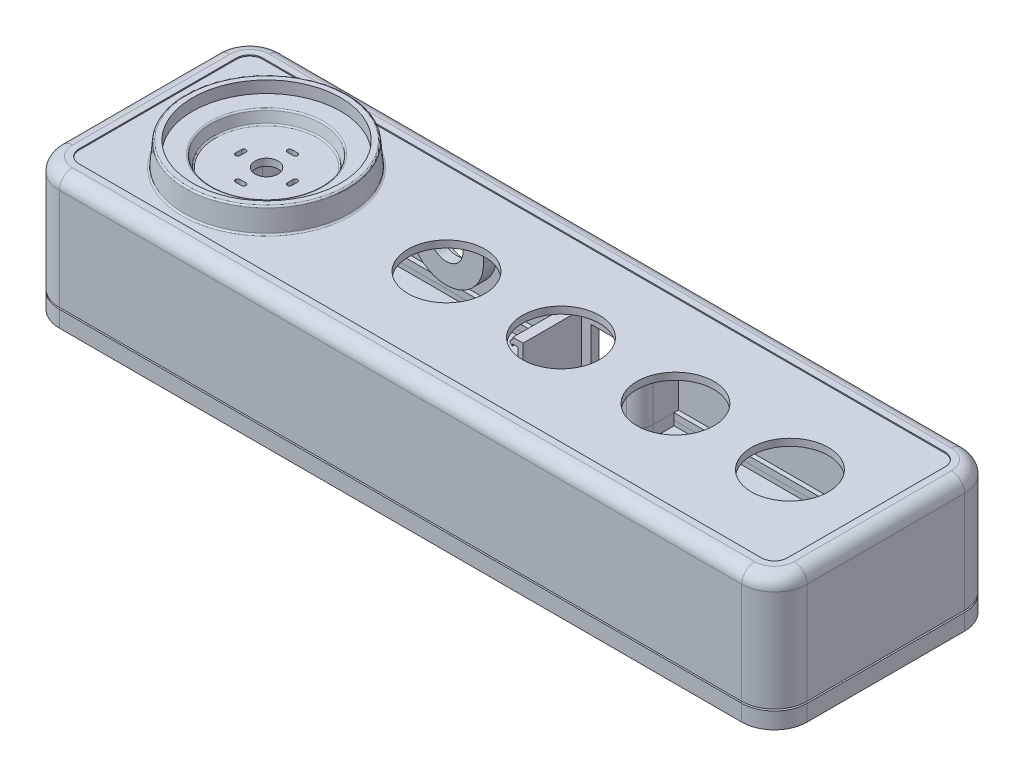
SolidWorks part; units mm, degrees
note: The reader was unsure of these and kept them because the rebuilt part matched: shared geometry of "Sketch11<3>", "Sketch18<3>".
ref_plane "Front Plane" through (0, 0, 0) normal (0, 0, 1) x (1, 0, 0)
ref_plane "Top Plane" through (0, 0, 0) normal (0, 1, 0) x (1, 0, 0)
ref_plane "Right Plane" through (0, 0, 0) normal (1, 0, 0) x (0, 0, -1)
sketch "Sketch1" plane through (0, 0, 0) normal (0, 1, 0) x (1, 0, 0)
  line L0 (0, 0) -> (55, 0) construction
  line L6 (55, 0) -> (90, 0) construction
  line L7 (90, 0) -> (125, 0) construction
  line L8 (125, 0) -> (160, 0) construction
  line L9 (107.5, 18.5) -> (107.5, 0) construction
  line L10 (72.5, 18.5) -> (72.5, 0) construction
  circle A0 centre (55, 0) radius 11.775
  circle A1 centre (90, 0) radius 11.775
  circle A2 centre (160, 0) radius 11.775
  circle A3 centre (125, 0) radius 11.775
  circle A4 centre (55, 0) radius 13.55 construction
  circle A5 centre (90, 0) radius 13.55 construction
  circle A6 centre (125, 0) radius 13.55 construction
  circle A7 centre (160, 0) radius 13.55 construction
  circle A8 centre (0, 0) radius 3.5
  circle A9 centre (0, 0) radius 23.5 construction
  circle A11 centre (72.5, 18.5) radius 6.365 construction
  circle A13 centre (107.5, 18.5) radius 6.365 construction
  dimension "D1" = 23.55
  dimension "D2" = 27.1
  dimension "D6" = 47
  dimension "D7" = 7
  dimension "D10" = 12.73
  dimension "D3" = 35
  dimension "D4" = 35
  dimension "D5" = 35
  dimension "D8" = 55
  dimension "D11" = 18.5
sketch "Sketch2" plane through (0, 0, 0) normal (0, 1, 0) x (1, 0, 0)
  line L0 (0, 0) -> (-39.2678, 0) construction
  line L1 (-29.2678, 34.0598) -> (179.3178, 34.0598)
  line L2 (-39.2678, 24.0598) -> (-39.2678, -24.0598)
  line L3 (-29.2678, -34.0598) -> (179.3178, -34.0598)
  line L4 (189.3178, 24.0598) -> (189.3178, -24.0598)
  circle A0 centre (0, 0) radius 23.5 construction
  circle A2 centre (160, 0) radius 13.55 construction
  arc A4 (179.3178, 34.0598) -> (189.3178, 24.0598) centre (179.3178, 24.0598) cw
  arc A5 (179.3178, -34.0598) -> (189.3178, -24.0598) centre (179.3178, -24.0598) ccw
  arc A6 (-39.2678, -24.0598) -> (-29.2678, -34.0598) centre (-29.2678, -24.0598) ccw
  arc A7 (-29.2678, 34.0598) -> (-39.2678, 24.0598) centre (-29.2678, 24.0598) ccw
  dimension "D3" = 10
  dimension "D1" = 15.7678
  dimension "D2" = 15.7678
extrude "Boss-Extrude1" add sketch "Sketch2" against normal blind 35
fillet "Fillet1" radius 4 8 edges at (-39.2678, 0, 0) (-36.3389, 0, -31.1309) (75.025, 0, -34.0598) (186.3889, 0, -31.1309) (189.3178, 0, 0) (186.3889, 0, 31.1309) (75.025, 0, 34.0598) (-36.3389, 0, 31.1309)
sketch "Sketch9" plane through (0, 0, 0) normal (0, 1, 0) x (1, 0, 0)
  line L8 (-33.2678, 24.0598) -> (-33.2678, -24.0598)
  line L9 (-29.2678, -28.0598) -> (179.3178, -28.0598)
  line L10 (183.3178, -24.0598) -> (183.3178, 24.0598)
  line L11 (179.3178, 28.0598) -> (-29.2678, 28.0598)
  line L12 (-33.2678, 24.0598) -> (-33.2678, -24.0598)
  line L13 (-29.2678, -28.0598) -> (179.3178, -28.0598)
  line L14 (183.3178, -24.0598) -> (183.3178, 24.0598)
  line L15 (179.3178, 28.0598) -> (-29.2678, 28.0598)
  arc A8 (-29.2678, 28.0598) -> (-33.2678, 24.0598) centre (-29.2678, 24.0598) ccw
  arc A9 (-33.2678, -24.0598) -> (-29.2678, -28.0598) centre (-29.2678, -24.0598) ccw
  arc A10 (179.3178, -28.0598) -> (183.3178, -24.0598) centre (179.3178, -24.0598) ccw
  arc A11 (183.3178, 24.0598) -> (179.3178, 28.0598) centre (179.3178, 24.0598) ccw
  arc A12 (-29.2678, 28.0598) -> (-33.2678, 24.0598) centre (-29.2678, 24.0598) ccw
  arc A13 (-33.2678, -24.0598) -> (-29.2678, -28.0598) centre (-29.2678, -24.0598) ccw
  arc A14 (179.3178, -28.0598) -> (183.3178, -24.0598) centre (179.3178, -24.0598) ccw
  arc A15 (183.3178, 24.0598) -> (179.3178, 28.0598) centre (179.3178, 24.0598) ccw
  dimension "D1" = 2
extrude "Cut-Extrude6" cut sketch "Sketch9" against normal blind 0.35
shell "Shell1" thickness 2.15
extrude "Cut-Extrude1" cut sketch "Sketch1" against normal through all both and the other way through all
sketch "Sketch6" plane through (0, 0, 0) normal (0, 1, 0) x (1, 0, 0)
  line L0 (7.9125, 0.9) -> (7.9125, -0.9) construction
  line L1 (8.6125, 0.9) -> (8.6125, -0.9)
  line L2 (7.2125, 0.9) -> (7.2125, -0.9)
  line L5 (7.3125, 0.8) -> (7.3125, -0.8) construction
  line L6 (8.5125, -0.8) -> (8.5125, 0.8) construction
  arc A0 (8.6125, 0.9) -> (7.2125, 0.9) centre (7.9125, 0.9) ccw
  arc A1 (7.2125, -0.9) -> (8.6125, -0.9) centre (7.9125, -0.9) ccw
  arc A4 (7.3125, -0.8) -> (8.5125, -0.8) centre (7.9125, -0.8) ccw construction
  arc A5 (8.5125, 0.8) -> (7.3125, 0.8) centre (7.9125, 0.8) ccw construction
  point P2 (7.9125, 0)
  dimension "D2" = 0.1
  dimension "D4" = 0.1
  dimension "D3" = 0.1
  dimension "D1" = 0.1
extrude "Cut-Extrude4" cut sketch "Sketch6" against normal through all both and the other way through all
sketch "Sketch7" plane through (0, 0, 0) normal (0, 0, 1) x (1, 0, 0)
  line L0 (0, 0) -> (0, 11.3) construction
  line L1 (-25.2782, -0.35) -> (-24.65, 6.83)
  line L3 (-24.65, 6.83) -> (-22.65, 6.83)
  line L4 (-22.65, 6.83) -> (-22.65, 3.23)
  line L5 (-22.65, 3.23) -> (-16.9593, 3.23)
  line L6 (-16.9593, 3.23) -> (-16, -0.35)
  line L7 (-16, -0.35) -> (-25.2782, -0.35)
  line L8 (-22.3, 3.58) -> (22.3, 3.58) construction
  line L9 (-22.3, 7.18) -> (-22.3, 3.58) construction
  line L10 (-22.3, 7.18) -> (22.3, 7.18) construction
  line L11 (-29.2678, -0.35) -> (179.3178, -0.35) construction
  dimension "D1" = 32
  dimension "D2" = 0.35
  dimension "D3" = 0.35
  dimension "D4" = 0.35
  dimension "D5" = 75
  dimension "D6" = 85
  dimension "D7" = 2
revolve "Revolve1" add sketch "Sketch7" angle 360 about L0
fillet "Fillet3" radius 0.5 4 edges at (0, 6.83, -24.65) (0, -0.35, -25.2782) (0, -0.35, -16) (0, 3.23, -16.9593)
pattern_circular "CirPattern1" count 4 over 360 about axis through (0, 0, 0) along (0, 1, 0) of "Cut-Extrude4"
sketch "Sketch11" plane through (0, -2.5, 0) normal (0, -1, 0) x (-1, 0, 0)
  circle A0 centre (-20.5822, -19) radius 2
  circle A1 centre (-33.5822, -19) radius 2
  circle A2 centre (-28.0822, -8.5) radius 2
  circle A3 centre (-28.0822, -8.5) radius 1.425
  circle A4 centre (-20.5822, -19) radius 1.425
  circle A5 centre (-33.5822, -19) radius 1.425
  circle A6 centre (-20.5822, 1) radius 2
  circle A7 centre (-33.5822, 1) radius 2
  dimension "D1" = 4
  dimension "D2" = 20
  dimension "D3" = 2.85
extrude "Boss-Extrude3" add sketch "Sketch11" along normal blind 2 contours A7 | A6 | A2 A3 | A3 | A4 | A0 A4 | A1 A5 | A5
extrude "Boss-Extrude4" add sketch "Sketch11<3>" along normal blind 4 contours A3 | A4 | A5
sketch "Sketch11<3>" plane through (0, -2.5, 0) normal (0, -1, 0) x (-1, 0, 0) same geometry as "Sketch11"
ref_plane "Plane1" through (25, 0, 0) normal (1, 0, 0) x (0, 0, -1)
sketch "Sketch13" plane through (25, 0, 0) normal (1, 0, 0) x (0, 0, -1)
  line L0 (-25.25, -2.5) -> (-25.25, -6.2)
  line L1 (24.0598, -2.5) -> (-24.0598, -2.5) construction
  line L2 (-25.25, -6.2) -> (-24, -6.2)
  line L3 (-24, -6.2) -> (-25.3, -7.5)
  line L4 (-25.3, -7.5) -> (-26.8, -7.5)
  line L5 (-26.8, -7.5) -> (-27.75, -2.5)
  line L6 (-27.75, -2.5) -> (-25.25, -2.5)
  line L7 (8.25, -2.5) -> (8.25, -6.2)
  line L8 (8.25, -6.2) -> (7, -6.2)
  line L9 (7, -6.2) -> (8.3, -7.5)
  line L10 (8.3, -7.5) -> (9.8, -7.5)
  line L11 (9.8, -7.5) -> (10.75, -2.5)
  line L12 (10.75, -2.5) -> (8.25, -2.5)
  line L13 (-25, -6.1) -> (-25, -4.5) construction
  line L14 (-25, -6.1) -> (-23, -6.1) construction
  line L15 (8, -6.1) -> (8, -4.5) construction
  dimension "D1" = 0.25
  dimension "D2" = 0.1
  dimension "D3" = 0.25
  dimension "D4" = 2.5
  dimension "D5" = 2.5
  dimension "D6" = 5
  dimension "D7" = 45
  dimension "D8" = 45
  dimension "D9" = 1.25
  dimension "D10" = 1.5
extrude "Boss-Extrude5" add sketch "Sketch13" along normal mid plane 3
sketch "Sketch15" plane through (0, -35, 0) normal (0, -1, 0) x (1, 0, 0)
  line L13 (-29.2678, -32.7598) -> (179.3178, -32.7598)
  line L14 (188.0178, -24.0598) -> (188.0178, 24.0598)
  line L15 (179.3178, 32.7598) -> (-29.2678, 32.7598)
  line L16 (-37.9678, 24.0598) -> (-37.9678, -24.0598)
  line L17 (-29.2678, -32.7598) -> (179.3178, -32.7598)
  line L18 (188.0178, -24.0598) -> (188.0178, 24.0598)
  line L19 (179.3178, 32.7598) -> (-29.2678, 32.7598)
  line L20 (-37.9678, 24.0598) -> (-37.9678, -24.0598)
  arc A12 (188.0178, 24.0598) -> (179.3178, 32.7598) centre (179.3178, 24.0598) ccw
  arc A13 (179.3178, -32.7598) -> (188.0178, -24.0598) centre (179.3178, -24.0598) ccw
  arc A14 (-37.9678, -24.0598) -> (-29.2678, -32.7598) centre (-29.2678, -24.0598) ccw
  arc A15 (-29.2678, 32.7598) -> (-37.9678, 24.0598) centre (-29.2678, 24.0598) ccw
  arc A16 (188.0178, 24.0598) -> (179.3178, 32.7598) centre (179.3178, 24.0598) ccw
  arc A17 (179.3178, -32.7598) -> (188.0178, -24.0598) centre (179.3178, -24.0598) ccw
  arc A18 (-37.9678, -24.0598) -> (-29.2678, -32.7598) centre (-29.2678, -24.0598) ccw
  arc A19 (-29.2678, 32.7598) -> (-37.9678, 24.0598) centre (-29.2678, 24.0598) ccw
  dimension "D1" = 0.85
extrude "Cut-Extrude8" cut sketch "Sketch15" against normal blind 1.5
sketch "Sketch16" plane through (0, -33.5, 0) normal (0, -1, 0) x (1, 0, 0)
  line L4 (-29.2678, -30.5098) -> (179.3178, -30.5098)
  line L5 (185.7678, -24.0598) -> (185.7678, 24.0598)
  line L6 (179.3178, 30.5098) -> (-29.2678, 30.5098)
  line L7 (-35.7178, 24.0598) -> (-35.7178, -24.0598)
  line L8 (-29.2678, -32.5098) -> (179.3178, -32.5098)
  line L9 (187.7678, -24.0598) -> (187.7678, 24.0598)
  line L10 (179.3178, 32.5098) -> (-29.2678, 32.5098)
  line L11 (-37.7178, 24.0598) -> (-37.7178, -24.0598)
  line L12 (-29.2678, -32.5098) -> (179.3178, -32.5098)
  line L13 (187.7678, -24.0598) -> (187.7678, 24.0598)
  line L14 (179.3178, 32.5098) -> (-29.2678, 32.5098)
  line L15 (-37.7178, 24.0598) -> (-37.7178, -24.0598)
  arc A4 (179.3178, -30.5098) -> (185.7678, -24.0598) centre (179.3178, -24.0598) ccw
  arc A5 (185.7678, 24.0598) -> (179.3178, 30.5098) centre (179.3178, 24.0598) ccw
  arc A6 (-29.2678, 30.5098) -> (-35.7178, 24.0598) centre (-29.2678, 24.0598) ccw
  arc A7 (-35.7178, -24.0598) -> (-29.2678, -30.5098) centre (-29.2678, -24.0598) ccw
  arc A8 (-37.7178, -24.0598) -> (-29.2678, -32.5098) centre (-29.2678, -24.0598) ccw
  arc A9 (179.3178, -32.5098) -> (187.7678, -24.0598) centre (179.3178, -24.0598) ccw
  arc A10 (187.7678, 24.0598) -> (179.3178, 32.5098) centre (179.3178, 24.0598) ccw
  arc A11 (-29.2678, 32.5098) -> (-37.7178, 24.0598) centre (-29.2678, 24.0598) ccw
  arc A12 (-37.7178, -24.0598) -> (-29.2678, -32.5098) centre (-29.2678, -24.0598) ccw
  arc A13 (179.3178, -32.5098) -> (187.7678, -24.0598) centre (179.3178, -24.0598) ccw
  arc A14 (187.7678, 24.0598) -> (179.3178, 32.5098) centre (179.3178, 24.0598) ccw
  arc A15 (-29.2678, 32.5098) -> (-37.7178, 24.0598) centre (-29.2678, 24.0598) ccw
  dimension "D1" = 0.25
  dimension "D2" = 2
extrude "Boss-Extrude6" add sketch "Sketch16" along normal blind 2 separate body
sketch "Sketch17" plane through (0, -35.5, 0) normal (0, -1, 0) x (1, 0, 0)
  line L0 (179.3178, -34.0598) -> (-29.2678, -34.0598) construction
  line L1 (189.3178, 24.0598) -> (189.3178, -24.0598) construction
  line L2 (-29.2678, 34.0598) -> (179.3178, 34.0598) construction
  line L3 (-39.2678, -24.0598) -> (-39.2678, 24.0598) construction
  line L4 (179.3178, -34.0598) -> (-29.2678, -34.0598)
  line L5 (189.3178, 24.0598) -> (189.3178, -24.0598)
  line L6 (-29.2678, 34.0598) -> (179.3178, 34.0598)
  line L7 (-39.2678, -24.0598) -> (-39.2678, 24.0598)
  arc A0 (-39.2678, -24.0598) -> (-29.2678, -34.0598) centre (-29.2678, -24.0598) ccw construction
  arc A1 (179.3178, -34.0598) -> (189.3178, -24.0598) centre (179.3178, -24.0598) ccw construction
  arc A2 (189.3178, 24.0598) -> (179.3178, 34.0598) centre (179.3178, 24.0598) ccw construction
  arc A3 (-29.2678, 34.0598) -> (-39.2678, 24.0598) centre (-29.2678, 24.0598) ccw construction
  arc A4 (-39.2678, -24.0598) -> (-29.2678, -34.0598) centre (-29.2678, -24.0598) ccw
  arc A5 (179.3178, -34.0598) -> (189.3178, -24.0598) centre (179.3178, -24.0598) ccw
  arc A6 (189.3178, 24.0598) -> (179.3178, 34.0598) centre (179.3178, 24.0598) ccw
  arc A7 (-29.2678, 34.0598) -> (-39.2678, 24.0598) centre (-29.2678, 24.0598) ccw
extrude "Boss-Extrude7" add sketch "Sketch17" along normal blind 5 separate body
shell "Shell2" thickness 3.5
combine bodies "Combine1" operation type add bodies to combine 117 116
sketch "Sketch18" plane through (0, -33.5, 0) normal (0, -1, 0) x (1, 0, 0)
  line L2 (-37.9678, 24.0598) -> (-37.9678, 20.0598)
  line L3 (-37.9678, 24.0598) -> (-37.9678, -24.0598) construction
  line L4 (-37.9678, 20.0598) -> (-29.2678, 20.0598)
  line L5 (-25.2678, 24.0598) -> (-25.2678, 32.7598)
  line L6 (179.3178, 32.7598) -> (-29.2678, 32.7598) construction
  line L7 (-25.2678, 32.7598) -> (-29.2678, 32.7598)
  line L8 (-28.2079, 22.9999) -> (-26.4394, 21.2314) construction
  line L9 (-30.1878, 24.9798) -> (-28.2079, 22.9999) construction
  arc A0 (-29.2678, 32.7598) -> (-37.9678, 24.0598) centre (-29.2678, 24.0598) ccw construction
  arc A1 (-29.2678, 32.7598) -> (-37.9678, 24.0598) centre (-29.2678, 24.0598) ccw
  circle A3 centre (-30.1878, 24.9798) radius 2.8
  arc A4 (-29.2678, 20.0598) -> (-25.2678, 24.0598) centre (-29.2678, 24.0598) ccw
  line M39 (-37.1178, -24.0598) -> (-37.1178, 24.0598)
  arc M40 (-37.1178, 24.0598) -> (-29.2678, 31.9098) centre (-29.2678, 24.0598) cw
  line M41 (-29.2678, 31.9098) -> (179.3178, 31.9098)
  dimension "D2" = 5.6
  dimension "D1" = 4
  dimension "D4" = 4
  dimension "D5" = 4.92
  dimension "D6" = 4.92
  dimension "D3" = 2.5011
extrude "Boss-Extrude8" add sketch "Sketch18" against normal blind 15 contours L4 A4 L5 A3 M41 M40 M39 | A3
extrude "Cut-Extrude9" cut sketch "Sketch18<3>" against normal blind 9.5 contours A3
sketch "Sketch18<3>" plane through (0, -33.5, 0) normal (0, -1, 0) x (1, 0, 0) same geometry as "Sketch18"
mirror "Mirror1" about plane through (0, 0, 0) normal (0, 0, 1) of "Boss-Extrude8", "Cut-Extrude9"
ref_plane "Plane2" through (75.0272, 0, 0) normal (-1, 0, 0) x (0, 0, 1)
mirror "Mirror2" about plane through (75.0272, 0, 0) normal (-1, 0, 0) of "Boss-Extrude8", "Cut-Extrude9", "Mirror1"
sketch "Sketch22" plane through (0, 0, -32.7598) normal (0, 0, 1) x (1, 0, 0)
  line L0 (67.5422, -35) -> (67.5422, -26.4884)
  line L1 (-29.2678, -35) -> (179.3178, -35) construction
  line L3 (82.5122, -26.4884) -> (82.5122, -35)
  line L4 (82.5122, -35) -> (67.5422, -35)
  line L8 (82.2622, -26.315) -> (82.2622, -38) construction
  line L9 (67.7922, -38) -> (67.7922, -26.315) construction
  arc A2 (67.5422, -26.4884) -> (82.5122, -26.4884) centre (75.0272, -26.4884) cw
  dimension "D1" = 0.25
  dimension "D2" = 8.5116
  dimension "D3" = 0.25
extrude "Cut-Extrude12" cut sketch "Sketch22" against normal blind 2.28 and the other way blind 2.28 contours L0 A2 L3 L4
sketch "Sketch25" plane through (0, 0, -34.0598) normal (0, 0, -1) x (-1, 0, 0)
  line L1 (-82.5122, -33.5) -> (-67.5422, -33.5)
  line L2 (-82.5122, -33.5) -> (-82.5122, -38.1)
  line L3 (-82.5122, -38.1) -> (-67.5422, -38.1)
  line L4 (-67.5422, -33.5) -> (-67.5422, -38.1)
  line L5 (-82.5122, -26.4884) -> (-82.5122, -35) construction
  line L6 (-67.5422, -35) -> (-67.5422, -26.4884) construction
  line L7 (-82.2622, -38) -> (-67.7922, -38) construction
  line L8 (29.2678, -33.5) -> (-179.3178, -33.5) construction
  dimension "D1" = 0.1
extrude "Cut-Extrude13" cut sketch "Sketch25" against normal blind 2.82
sketch "Sketch26" plane through (0, 0, -30.5598) normal (0, 0, 1) x (1, 0, 0)
  line L0 (-29.2678, -37) -> (179.3178, -37) construction
  line L1 (70.5922, -31.85) -> (79.4622, -31.85)
  line L2 (70.5922, -31.85) -> (70.5922, -37)
  line L3 (70.5922, -37) -> (79.4622, -37)
  line L4 (79.4622, -31.85) -> (79.4622, -37)
  line L5 (70.5922, -31.75) -> (70.5922, -25.395) construction
  line L6 (79.4622, -25.395) -> (79.4622, -31.75) construction
  line L7 (79.4622, -31.75) -> (70.5922, -31.75) construction
  dimension "D1" = 0.1
extrude "Boss-Extrude13" add sketch "Sketch26" along normal blind 1.9
sketch "Sketch27" plane through (0, 0, -30.5598) normal (0, 0, -1) x (-1, 0, 0)
  line L4 (-79.4622, -31.85) -> (-79.4622, -33.5)
  line L5 (-79.4622, -33.5) -> (-70.5922, -33.5)
  line L6 (-70.5922, -33.5) -> (-70.5922, -31.85)
  line L7 (-70.5922, -31.85) -> (-79.4622, -31.85)
  line L8 (-79.4622, -31.85) -> (-79.4622, -33.5)
  line L9 (-79.4622, -33.5) -> (-70.5922, -33.5)
  line L10 (-70.5922, -33.5) -> (-70.5922, -31.85)
  line L11 (-70.5922, -31.85) -> (-79.4622, -31.85)
  dimension "D1" = 0
extrude "Boss-Extrude14" add sketch "Sketch27" along normal up to surface (0.68 mm away) up to face at (75.0272, -35.8, -31.2398)
sketch "Sketch29" plane through (0, 0, -34.0598) normal (0, 0, -1) x (-1, 0, 0)
  line L0 (-27.0159, -20.5368) -> (7.1178, -20.5368) construction
  line L1 (29.2678, -4) -> (-179.3178, -4) construction
  line L2 (37.1178, -18.5) -> (37.1178, -4) construction
  circle A0 centre (7.1178, -20.5368) radius 3.5
  circle A1 centre (-27.0159, -20.5368) radius 5.14
  dimension "D2" = 7
  dimension "D3" = 10.28
  dimension "D1" = 16.5368
  dimension "D4" = 34.1337
  dimension "D5" = 30
extrude "Cut-Extrude14" cut sketch "Sketch29" against normal up to next (2.15 mm away)
sketch "Sketch30" plane through (0, 0, -31.9098) normal (0, 0, 1) x (1, 0, 0)
  line L0 (-0.6178, -20.5368) -> (15.6259, -20.5368)
  line L1 (-13.6178, -20.5368) -> (-13.6178, -4)
  line L2 (-29.2678, -4) -> (179.3178, -4) construction
  line L3 (-13.6178, -4) -> (38.4059, -4)
  line L4 (38.4059, -4) -> (38.4059, -20.5368)
  arc A0 (-13.6178, -20.5368) -> (-0.6178, -20.5368) centre (-7.1178, -20.5368) ccw
  arc A1 (15.6259, -20.5368) -> (38.4059, -20.5368) centre (27.0159, -20.5368) ccw
  circle A2 centre (-7.1178, -20.5368) radius 3.5
  circle A3 centre (27.0159, -20.5368) radius 5.14
  circle A4 centre (27.0159, -20.5368) radius 5.14 construction
  circle A5 centre (-7.1178, -20.5368) radius 3.5 construction
  dimension "D1" = 3
  dimension "D2" = 6.25
extrude "Boss-Extrude15" add sketch "Sketch30" along normal blind 4
sketch "Sketch31" plane through (0, 0, -27.9098) normal (0, 0, 1) x (1, 0, 0)
  line L0 (-8.0428, -12.7177) -> (-6.1928, -12.7177) construction
  line L1 (-8.0428, -12.0327) -> (-6.1928, -12.0327)
  line L2 (-8.0428, -13.4027) -> (-6.1928, -13.4027)
  line L3 (27.0159, -20.5368) -> (27.0159, -11.0368) construction
  line L4 (-7.1178, -20.5368) -> (-7.1178, -12.7177) construction
  line L5 (-6.3428, -13.2527) -> (-7.8928, -13.2527) construction
  line L6 (-7.8928, -12.1827) -> (-6.3428, -12.1827) construction
  circle A0 centre (27.0159, -11.0368) radius 1.65
  arc A1 (-8.0428, -12.0327) -> (-8.0428, -13.4027) centre (-8.0428, -12.7177) ccw
  arc A2 (-6.1928, -13.4027) -> (-6.1928, -12.0327) centre (-6.1928, -12.7177) ccw
  arc A3 (28.1853, -11.9763) -> (25.8466, -11.9763) centre (27.0159, -11.0368) ccw construction
  arc A4 (-7.9978, -12.1931) -> (-7.8928, -13.2527) centre (-7.8928, -12.7177) ccw construction
  point P4 (-7.1178, -12.7177)
  dimension "D1" = 0.15
  dimension "D4" = 0.15
  dimension "D2" = 0.15
  dimension "D3" = 0.15
extrude "Cut-Extrude15" cut sketch "Sketch31" against normal blind 3
sketch "Sketch32" plane through (0, 0, -34.0598) normal (0, 0, -1) x (-1, 0, 0)
  circle A0 centre (-27.0159, -20.5368) radius 8
  circle A1 centre (7.1178, -20.5368) radius 6.075
  dimension "D1" = 16
  dimension "D2" = 12.15
extrude "Cut-Extrude16" cut sketch "Sketch32" against normal blind 3
sketch "Sketch33" plane through (0, -2.5, 0) normal (0, -1, 0) x (1, 0, 0)
  line L0 (67.5422, -31.9098) -> (67.5422, -31.1798)
  line L1 (67.5422, -31.1798) -> (70.4922, -31.1798)
  line L2 (70.4922, -31.1798) -> (70.4922, -28.6698)
  line L3 (70.4922, -28.6698) -> (66.0422, -28.6698)
  line L4 (66.0422, -28.6698) -> (66.0422, -31.9098)
  line L5 (67.5422, -31.9098) -> (-25.2678, -31.9098) construction
  line L6 (66.0422, -31.9098) -> (67.5422, -31.9098)
  line L7 (82.5122, -31.9098) -> (82.5122, -31.1798)
  line L8 (82.5122, -31.1798) -> (79.5622, -31.1798)
  line L9 (79.5622, -31.1798) -> (79.5622, -28.6698)
  line L10 (79.5622, -28.6698) -> (84.0122, -28.6698)
  line L11 (84.0122, -28.6698) -> (84.0122, -31.9098)
  line L12 (175.3222, -31.9098) -> (82.5122, -31.9098) construction
  line L13 (84.0122, -31.9098) -> (82.5122, -31.9098)
  line L14 (82.2622, -31.2798) -> (67.7922, -31.2798) construction
  line L15 (67.6922, -28.5698) -> (82.3622, -28.5698) construction
  line L16 (79.4622, -31.2798) -> (79.4622, -28.5698) construction
  dimension "D1" = 0.1
  dimension "D2" = 0.1
  dimension "D3" = 0.1
  dimension "D4" = 1.5
extrude "Boss-Extrude16" add sketch "Sketch33" along normal up to surface (31 mm away) up to face at (75.0262, -33.5, -4.6193)
sketch "Sketch34" plane through (0, -2.5, 0) normal (0, -1, 0) x (1, 0, 0)
  line L0 (70.4922, -28.6698) -> (66.0422, -28.6698) construction
  line L1 (70.4922, -28.6698) -> (79.5622, -28.6698)
  line L2 (70.4922, -28.6698) -> (70.4922, -31.1798)
  line L3 (70.4922, -31.1798) -> (79.5622, -31.1798)
  line L4 (79.5622, -28.6698) -> (79.5622, -31.1798)
  line L5 (70.4922, -31.1798) -> (70.4922, -28.6698) construction
extrude "Boss-Extrude17" add sketch "Sketch34" along normal up to vertex (84.607 mm away)
sketch "Sketch35" plane through (0, 0, -31.1798) normal (0, 0, -1) x (-1, 0, 0)
  line L0 (-82.5122, -26.4884) -> (-82.5122, -2.5276)
  line L1 (-82.5122, -2.5276) -> (-67.5422, -2.5276)
  line L2 (-67.5422, -2.5276) -> (-67.5422, -26.4884)
  arc A0 (-67.5422, -26.4884) -> (-82.5122, -26.4884) centre (-75.0272, -26.4884) ccw construction
  arc A1 (-67.5422, -26.4884) -> (-82.5122, -26.4884) centre (-75.0272, -26.4884) ccw
extrude "Boss-Extrude18" add sketch "Sketch35" along normal blind 2
sketch "Sketch36" plane through (0, 0, -31.9098) normal (0, 0, 1) x (1, 0, 0)
  line L0 (66.0422, -33.5) -> (66.0422, -4) construction
  line L1 (66.0422, -20.4) -> (64.3422, -20.4)
  line L2 (66.0422, -20.4) -> (66.0422, -31.6)
  line L3 (66.0422, -31.6) -> (64.3422, -31.6)
  line L4 (64.3422, -20.4) -> (64.3422, -31.6)
  line L5 (64.4422, -31.5) -> (66.0422, -31.5) construction
  line L6 (64.4422, -21.5) -> (64.4422, -30.5) construction
  line L7 (64.4422, -20.5) -> (66.0422, -20.5) construction
  dimension "D1" = 0.1
  dimension "D2" = 0.1
  dimension "D3" = 0.1
extrude "Cut-Extrude17" cut sketch "Sketch36" against normal blind 0.45
sketch "Sketch37" plane through (0, 0, -31.9098) normal (0, 0, 1) x (1, 0, 0)
  line L0 (64.4422, -20.5) -> (64.4422, -21.5) construction
  line L1 (64.4422, -20.745) -> (59.3422, -20.745)
  line L2 (64.4422, -20.745) -> (64.4422, -27.015)
  line L3 (64.4422, -27.015) -> (59.3422, -27.015)
  line L4 (59.3422, -20.745) -> (59.3422, -27.015)
  line L5 (59.4422, -20.845) -> (64.4422, -20.845) construction
  line L6 (59.4422, -20.845) -> (59.4422, -26.915) construction
  line L7 (59.4422, -26.915) -> (64.4422, -26.915) construction
  dimension "D1" = 0.1
  dimension "D2" = 0.1
  dimension "D3" = 0.1
extrude "Cut-Extrude18" cut sketch "Sketch37" against normal blind 0.2
sketch "Sketch38" plane through (0, 0, -34.0598) normal (0, 0, -1) x (-1, 0, 0)
  circle A0 centre (-61.9422, -23.88) radius 2.64
  circle A1 centre (-61.9422, -23.88) radius 2.49 construction
  dimension "D1" = 0.15
extrude "Cut-Extrude19" cut sketch "Sketch38" against normal up to next
sketch "Sketch39" plane through (66.0422, 0, 0) normal (1, 0, 0) x (0, 0, -1)
  line L2 (31.9098, -33.5) -> (10.8498, -33.5)
  line L3 (31.9098, -33.5) -> (31.9098, -18.5)
  line L4 (31.9098, -18.5) -> (10.8498, -18.5)
  line L5 (10.8498, -33.5) -> (10.8498, -18.5)
  line L6 (7.3498, -20.5) -> (31.3498, -20.5) construction
  circle A0 centre (13.8498, -26.75) radius 1.25 construction
  dimension "D1" = 3
  dimension "D2" = 2
extrude "Boss-Extrude19" add sketch "Sketch39" along normal blind 1.5
sketch "Sketch40" plane through (66.0422, 0, 0) normal (-1, 0, 0) x (0, 0, 1)
  circle A0 centre (-13.8498, -26.75) radius 1.13
  circle A1 centre (-13.8498, -26.75) radius 1.25 construction
  dimension "D1" = 0.12
extrude "Boss-Extrude20" add sketch "Sketch40" along normal blind 2
sketch "Sketch41" plane through (66.0422, 0, 0) normal (-1, 0, 0) x (0, 0, 1)
  line L0 (-31.9098, -18.5) -> (-31.9098, -33.5) construction
  line L1 (-10.8498, -18.5) -> (-31.9098, -18.5)
  line L2 (-10.8498, -18.5) -> (-10.8498, -20.3)
  line L3 (-10.8498, -20.3) -> (-31.9098, -20.3)
  line L4 (-31.9098, -18.5) -> (-31.9098, -20.3)
  line L5 (-31.1798, -33.5) -> (-31.1798, -26.4884) construction
  line L6 (-10.8498, -33.5) -> (-31.1798, -33.5)
  line L7 (-10.8498, -33.5) -> (-10.8498, -31.7)
  line L8 (-10.8498, -31.7) -> (-31.1798, -31.7)
  line L9 (-31.1798, -33.5) -> (-31.1798, -31.7)
  line L10 (-7.3498, -20.5) -> (-31.3498, -20.5) construction
  line L11 (-31.3498, -31.5) -> (-7.3498, -31.5) construction
  dimension "D1" = 0.2
  dimension "D2" = 0.2
extrude "Boss-Extrude21" add sketch "Sketch41" along normal blind 1.6
sketch "Sketch42" plane through (0, 0, -10.8498) normal (0, 0, 1) x (1, 0, 0)
  line L0 (64.4422, -31.7) -> (64.3422, -31.7)
  line L1 (64.3422, -31.7) -> (64.3422, -31.15)
  line L2 (64.3422, -31.15) -> (64.1422, -31.15)
  line L3 (64.1422, -31.15) -> (63.5922, -31.75)
  line L4 (63.5922, -31.75) -> (63.5922, -32.25)
  line L5 (63.5922, -32.25) -> (64.4422, -33)
  line L6 (64.4422, -33.5) -> (64.4422, -31.7) construction
  line L7 (64.4422, -33) -> (64.4422, -31.7)
  line L8 (66.0422, -26) -> (57.8062, -26) construction
  line L9 (64.4422, -19) -> (64.4422, -20.3)
  line L10 (63.5922, -19.75) -> (64.4422, -19)
  line L11 (63.5922, -20.25) -> (63.5922, -19.75)
  line L12 (64.1422, -20.85) -> (63.5922, -20.25)
  line L13 (64.3422, -20.85) -> (64.1422, -20.85)
  line L14 (64.3422, -20.3) -> (64.3422, -20.85)
  line L15 (64.4422, -20.3) -> (64.3422, -20.3)
  line L16 (64.4422, -30.5) -> (64.4422, -31.5) construction
  dimension "D1" = 0.1
  dimension "D2" = 0.55
  dimension "D3" = 0.85
  dimension "D4" = 0.75
  dimension "D5" = 1.3
  dimension "D6" = 0.2
  dimension "D7" = 0.5
extrude "Boss-Extrude22" add sketch "Sketch42" against normal blind 1.6
sketch "Sketch45" plane through (0, -33.5, 0) normal (0, -1, 0) x (1, 0, 0)
  line L0 (175.3222, -31.9098) -> (84.0122, -31.9098) construction
  line L1 (84.0122, -31.9098) -> (94.0122, -31.9098)
  line L2 (84.0122, -31.9098) -> (84.0122, -24.0598)
  line L3 (88.0122, -20.0598) -> (90.0122, -20.0598)
  line L4 (94.0122, -31.9098) -> (94.0122, -24.0598)
  line L5 (187.1678, -20.0598) -> (179.3222, -20.0598) construction
  line L7 (70.025, 32.7598) -> (80.025, 32.7598)
  line L8 (70.025, 32.7598) -> (70.025, 24.0598)
  line L9 (74.025, 20.0598) -> (76.025, 20.0598)
  line L10 (80.025, 32.7598) -> (80.025, 24.0598)
  line L11 (84.0122, -31.9098) -> (84.0122, -28.6698) construction
  line L12 (187.1678, 20.0598) -> (179.3222, 20.0598) construction
  line L13 (75.025, 30.2098) -> (75.025, 16.3135) construction
  line L14 (179.3178, 30.2098) -> (-29.2678, 30.2098) construction
  line L16 (179.3178, 32.7598) -> (-29.2678, 32.7598) construction
  arc A0 (90.0122, -20.0598) -> (94.0122, -24.0598) centre (90.0122, -24.0598) cw
  arc A1 (84.0122, -24.0598) -> (88.0122, -20.0598) centre (88.0122, -24.0598) cw
  arc A2 (76.025, 20.0598) -> (80.025, 24.0598) centre (76.025, 24.0598) ccw
  arc A3 (70.025, 24.0598) -> (74.025, 20.0598) centre (74.025, 24.0598) ccw
  point P10 (94.0122, -20.0598)
  point P13 (84.0122, -20.0598)
  point P24 (80.025, 20.0598)
  point P27 (70.025, 20.0598)
  dimension "D2" = 4
  dimension "D4" = 4
  dimension "D1" = 10
  dimension "D3" = 10
extrude "Boss-Extrude23" add sketch "Sketch45" against normal up to surface (15 mm away) up to face at (180.5341, -18.5, 26.3949)
sketch "Sketch46" plane through (0, -33.5, 0) normal (0, -1, 0) x (1, 0, 0)
  line L0 (-30.1878, 24.9798) -> (75.025, 24.9798) construction
  line L1 (180.2422, -24.9798) -> (89.0122, -24.9798) construction
  line L2 (75.025, 20.0598) -> (75.025, 24.9798) construction
  line L3 (74.025, 20.0598) -> (76.025, 20.0598) construction
  line L4 (89.0122, -24.9798) -> (89.0122, -20.0598) construction
  line L5 (90.0122, -20.0598) -> (88.0122, -20.0598) construction
  circle A0 centre (75.025, 24.9798) radius 2.8
  circle A1 centre (89.0122, -24.9798) radius 2.8
  circle A2 centre (-30.1878, 24.9798) radius 2.8 construction
extrude "Cut-Extrude21" cut sketch "Sketch46" against normal up to surface (9.5 mm away) up to face at (-30.1878, -24, -22.1798)
sketch "Sketch47" plane through (0, -37, 0) normal (0, 1, 0) x (1, 0, 0)
  line L2 (84.0122, 30.2098) -> (84.0122, 28.6698) construction
  line L3 (84.0122, 28.6698) -> (84.0122, 24.0598) construction
  line L5 (88.0122, 20.0598) -> (90.0122, 20.0598) construction
  line L6 (94.0122, 24.0598) -> (94.0122, 31.9098) construction
  line L7 (80.025, -31.9098) -> (80.025, -24.0598) construction
  line L12 (76.025, -20.0598) -> (74.025, -20.0598) construction
  line L13 (70.025, -24.0598) -> (70.025, -31.9098) construction
  line L14 (187.1678, 20.0598) -> (179.3222, 20.0598) construction
  line L15 (175.3222, 24.0598) -> (175.3222, 31.9098) construction
  line L16 (187.1678, -20.0598) -> (179.3222, -20.0598) construction
  line L17 (175.3222, -24.0598) -> (175.3222, -31.9098) construction
  line L18 (-25.2678, 24.0598) -> (-25.2678, 31.9098) construction
  line L19 (-37.1178, 20.0598) -> (-29.2678, 20.0598) construction
  line L20 (-25.2678, -24.0598) -> (-25.2678, -31.9098) construction
  line L21 (-37.1178, -20.0598) -> (-29.2678, -20.0598) construction
  line L22 (84.0122, 30.2098) -> (84.0122, 28.6698)
  line L23 (84.0122, 28.6698) -> (84.0122, 24.0598)
  line L24 (88.0122, 20.0598) -> (90.0122, 20.0598)
  line L25 (94.0122, 24.0598) -> (94.0122, 30.5598)
  line L26 (80.025, -30.5598) -> (80.025, -24.0598)
  line L27 (76.025, -20.0598) -> (74.025, -20.0598)
  line L28 (70.025, -24.0598) -> (70.025, -30.5598)
  line L29 (185.8178, 20.0598) -> (179.3222, 20.0598)
  line L30 (175.3222, 24.0598) -> (175.3222, 30.5598)
  line L31 (185.8178, -20.0598) -> (179.3222, -20.0598)
  line L32 (175.3222, -24.0598) -> (175.3222, -30.5598)
  line L33 (-25.2678, 24.0598) -> (-25.2678, 30.5598)
  line L34 (-35.7678, 20.0598) -> (-29.2678, 20.0598)
  line L35 (-25.2678, -24.0598) -> (-25.2678, -30.5598)
  line L36 (-35.7678, -20.0598) -> (-29.2678, -20.0598)
  line L37 (-35.7678, -20.0598) -> (-35.7678, -24.0598)
  line L38 (94.0122, 30.5598) -> (84.0122, 30.5598)
  line L39 (84.0122, 30.2098) -> (84.0122, 30.5598)
  line L40 (185.8178, 20.0598) -> (185.8178, 24.0598)
  line L41 (175.3222, -30.5598) -> (179.3178, -30.5598)
  line L42 (70.025, -30.5598) -> (80.025, -30.5598)
  line L45 (70.5922, 28.6598) -> (70.5922, 30.5598)
  line L46 (70.5922, 30.5598) -> (-29.2678, 30.5598)
  line L47 (-35.7678, 24.0598) -> (-35.7678, -24.0598)
  line L48 (-29.2678, -30.5598) -> (179.3178, -30.5598)
  line L49 (185.8178, -24.0598) -> (185.8178, 24.0598)
  line L50 (179.3178, 30.5598) -> (79.4622, 30.5598)
  line L51 (79.4622, 30.5598) -> (79.4622, 28.6598)
  line L52 (79.4622, 28.6598) -> (70.5922, 28.6598)
  line L54 (-25.2678, 30.5598) -> (-29.2678, 30.5598)
  line L55 (-35.7678, 24.0598) -> (-35.7678, 20.0598)
  line L56 (-29.2678, -30.5598) -> (-25.2678, -30.5598)
  line L57 (185.8178, -24.0598) -> (185.8178, -20.0598)
  line L58 (179.3178, 30.5598) -> (175.3222, 30.5598)
  arc A2 (84.0122, 24.0598) -> (88.0122, 20.0598) centre (88.0122, 24.0598) ccw construction
  arc A3 (90.0122, 20.0598) -> (94.0122, 24.0598) centre (90.0122, 24.0598) ccw construction
  arc A12 (80.025, -24.0598) -> (76.025, -20.0598) centre (76.025, -24.0598) ccw construction
  arc A13 (74.025, -20.0598) -> (70.025, -24.0598) centre (74.025, -24.0598) ccw construction
  arc A14 (175.3222, 24.0598) -> (179.3222, 20.0598) centre (179.3222, 24.0598) ccw construction
  arc A15 (179.3222, -20.0598) -> (175.3222, -24.0598) centre (179.3222, -24.0598) ccw construction
  arc A16 (-29.2678, 20.0598) -> (-25.2678, 24.0598) centre (-29.2678, 24.0598) ccw construction
  arc A17 (-25.2678, -24.0598) -> (-29.2678, -20.0598) centre (-29.2678, -24.0598) ccw construction
  arc A18 (84.0122, 24.0598) -> (88.0122, 20.0598) centre (88.0122, 24.0598) ccw
  arc A19 (90.0122, 20.0598) -> (94.0122, 24.0598) centre (90.0122, 24.0598) ccw
  arc A20 (80.025, -24.0598) -> (76.025, -20.0598) centre (76.025, -24.0598) ccw
  arc A21 (74.025, -20.0598) -> (70.025, -24.0598) centre (74.025, -24.0598) ccw
  arc A22 (175.3222, 24.0598) -> (179.3222, 20.0598) centre (179.3222, 24.0598) ccw
  arc A23 (179.3222, -20.0598) -> (175.3222, -24.0598) centre (179.3222, -24.0598) ccw
  arc A24 (-29.2678, 20.0598) -> (-25.2678, 24.0598) centre (-29.2678, 24.0598) ccw
  arc A25 (-25.2678, -24.0598) -> (-29.2678, -20.0598) centre (-29.2678, -24.0598) ccw
  arc A30 (-29.2678, 30.5598) -> (-35.7678, 24.0598) centre (-29.2678, 24.0598) ccw
  arc A31 (-35.7678, -24.0598) -> (-29.2678, -30.5598) centre (-29.2678, -24.0598) ccw
  arc A32 (179.3178, -30.5598) -> (185.8178, -24.0598) centre (179.3178, -24.0598) ccw
  arc A33 (185.8178, 24.0598) -> (179.3178, 30.5598) centre (179.3178, 24.0598) ccw
  arc A34 (-29.2678, 30.5598) -> (-35.7678, 24.0598) centre (-29.2678, 24.0598) ccw
  arc A35 (-35.7678, -24.0598) -> (-29.2678, -30.5598) centre (-29.2678, -24.0598) ccw
  arc A36 (179.3178, -30.5598) -> (185.8178, -24.0598) centre (179.3178, -24.0598) ccw
  arc A37 (185.8178, 24.0598) -> (179.3178, 30.5598) centre (179.3178, 24.0598) ccw
  dimension "D1" = 0
extrude "Boss-Extrude25" add sketch "Sketch47" along normal up to surface (3.5 mm away) up to face at (75.0257, -33.5, -10.4583)
hole_wizard "CSK for M4 Flat Head Machine Screw1" positions "Sketch48" profile "Sketch49" countersink size "M4" standard "ANSI Metric" end condition through all
sketch "Sketch48" plane through (0, -40.5, 0) normal (0, -1, 0) x (-1, 0, 0)
  point P0 (-180.2422, 24.9798)
  point P3 (-180.2422, -24.9798)
  point P6 (-89.0122, 24.9798)
  point P9 (-75.025, -24.9798)
  point P12 (30.1878, -24.9798)
  point P15 (30.1878, 24.9798)
sketch "Sketch49" plane through (180.2422, -40.5, -24.9798) normal (1, 0, 0) x (0, 0, -1)
  line L0 (0, 0) -> (0, 47.33)
  line L1 (0, 47.33) -> (2.25, 47.33)
  line L2 (2.25, 47.33) -> (2.25, 2.45)
  line L3 (2.25, 2.45) -> (4.7, 0)
  line L5 (4.7, 0) -> (0, 0)
  line L6 (-2.25, 2.45) -> (-4.7, 0) construction
  line L11 (0, -6.35) -> (0, 107.95) construction
  dimension "Thru Hole Dia." = 4.5
  dimension "Thru Hole Depth" = 47.33
  dimension "Near C'Sink Dia." = 9.4
  dimension "Near C'Sink Angle" = 90
equation "\"D4@Sketch1\"=\"D3@Sketch1\""
equation "\"D2@Sketch2\"=\"D1@Sketch2\""
equation "\"D5@Sketch18\"=\"D6@Sketch18\""
